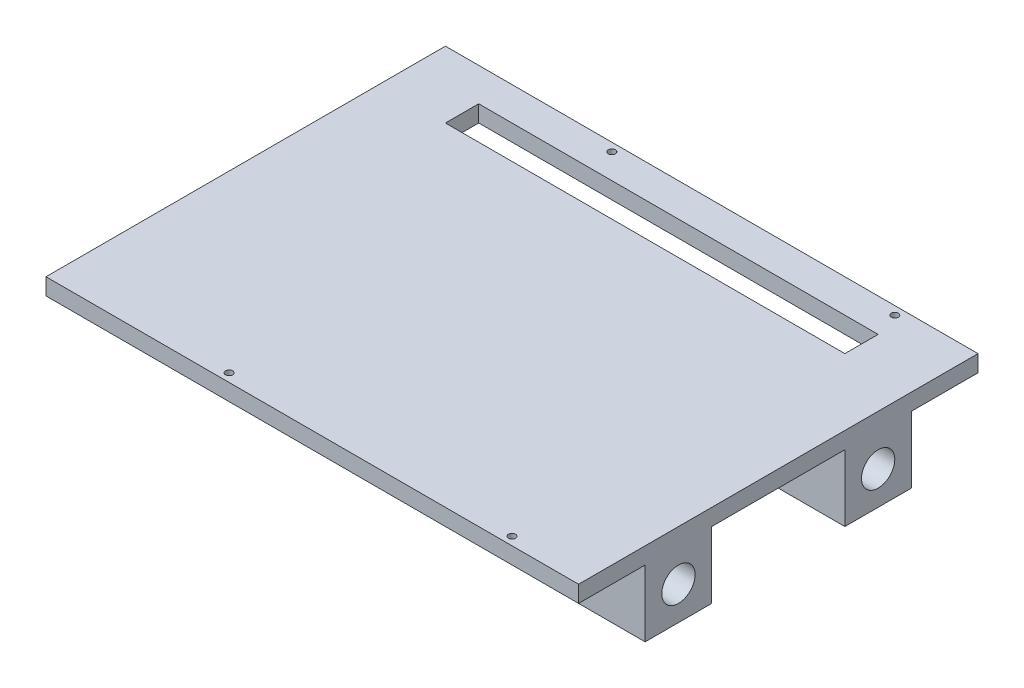
SolidWorks part; units mm, degrees
ref_plane "Front Plane" through (0, 0, 0) normal (0, 0, 1) x (1, 0, 0)
ref_plane "Top Plane" through (0, 0, 0) normal (0, 1, 0) x (1, 0, 0)
ref_plane "Right Plane" through (0, 0, 0) normal (1, 0, 0) x (0, 0, -1)
sketch "Sketch2" plane through (0, 0, 0) normal (0, 1, 0) x (1, 0, 0)
  line L1 (-101.6, -76.2) -> (101.6, -76.2)
  line L2 (-101.6, -76.2) -> (-101.6, 76.2)
  line L3 (-101.6, 76.2) -> (101.6, 76.2)
  line L4 (101.6, -76.2) -> (101.6, 76.2)
  line L5 (-101.6, -76.2) -> (101.6, 76.2) construction
  line L6 (-101.6, 76.2) -> (101.6, -76.2) construction
  point P0 (0, 0)
  dimension "D1" = 203.2
  dimension "D2" = 152.4
extrude "Boss-Extrude1" add sketch "Sketch2" along normal blind 6.35
sketch "Sketch3" plane through (0, 6.35, 0) normal (0, 1, 0) x (1, 0, 0)
  line L0 (-101.6, 0) -> (101.6, 0) construction
  line L1 (-101.6, 76.2) -> (-101.6, -76.2) construction
  line L2 (101.6, -76.2) -> (101.6, 76.2) construction
  line L3 (0, 76.2) -> (0, -76.2) construction
  line L4 (101.6, 76.2) -> (-101.6, 76.2) construction
  line L5 (-101.6, -76.2) -> (101.6, -76.2) construction
  line L7 (-76.2, 63.5) -> (76.2, 63.5)
  line L8 (-76.2, 63.5) -> (-76.2, 50.8)
  line L9 (-76.2, 50.8) -> (76.2, 50.8)
  line L10 (76.2, 63.5) -> (76.2, 50.8)
  line L11 (-76.2, 63.5) -> (76.2, 50.8) construction
  line L12 (-76.2, 50.8) -> (76.2, 63.5) construction
  point P12 (0, 57.15)
  dimension "D1" = 12.7
  dimension "D2" = 152.4
  dimension "D3" = 12.7
extrude "Cut-Extrude1" cut sketch "Sketch3" against normal blind 6.35
sketch "Sketch4" plane through (0, 0, 0) normal (0, -1, 0) x (1, 0, 0)
  line L0 (-101.6, -76.2) -> (-101.6, 76.2) construction
  line L1 (-101.6, 50.8) -> (-50.8, 50.8)
  line L2 (-101.6, 50.8) -> (-101.6, 25.4)
  line L3 (-101.6, 25.4) -> (-50.8, 25.4)
  line L4 (-50.8, 50.8) -> (-50.8, 25.4)
  line L5 (0, 76.2) -> (0, -76.2) construction
  line L6 (-101.6, 76.2) -> (101.6, 76.2) construction
  line L7 (101.6, -76.2) -> (-101.6, -76.2) construction
  line L8 (-101.6, 0) -> (101.6, 0) construction
  line L9 (101.6, 76.2) -> (101.6, -76.2) construction
  line L10 (101.6, 25.4) -> (50.8, 25.4)
  line L11 (50.8, 50.8) -> (50.8, 25.4)
  line L12 (101.6, 50.8) -> (50.8, 50.8)
  line L13 (101.6, 50.8) -> (101.6, 25.4)
  line L14 (101.6, -50.8) -> (101.6, -25.4)
  line L15 (101.6, -50.8) -> (50.8, -50.8)
  line L16 (50.8, -50.8) -> (50.8, -25.4)
  line L17 (101.6, -25.4) -> (50.8, -25.4)
  line L18 (-101.6, -25.4) -> (-50.8, -25.4)
  line L19 (-50.8, -50.8) -> (-50.8, -25.4)
  line L20 (-101.6, -50.8) -> (-50.8, -50.8)
  line L21 (-101.6, -50.8) -> (-101.6, -25.4)
  dimension "D1" = 25.4
  dimension "D2" = 50.8
  dimension "D3" = 25.4
sketch "Sketch6" plane through (0, 0, 0) normal (0, -1, 0) x (1, 0, 0)
  line L0 (0, -50.8) -> (0, -63.5) construction
  line L1 (-76.2, -50.8) -> (76.2, -50.8) construction
  line L2 (76.2, -63.5) -> (-76.2, -63.5) construction
extrude "Boss-Extrude2" add sketch "Sketch4" along normal blind 25.4
sketch "Sketch7" plane through (-101.6, 0, 0) normal (-1, 0, 0) x (0, 0, 1)
  line L0 (-38.1, -25.4) -> (-38.1, 6.35) construction
  line L1 (-25.4, -25.4) -> (-50.8, -25.4) construction
  line L2 (-76.2, 6.35) -> (76.2, 6.35) construction
  line L3 (-50.8, -12.7) -> (-25.4, -12.7) construction
  line L4 (-50.8, -25.4) -> (-50.8, 0) construction
  line L5 (-25.4, -25.4) -> (-25.4, 0) construction
  line L6 (38.1, -25.4) -> (38.1, 6.35) construction
  line L7 (50.8, -25.4) -> (25.4, -25.4) construction
  line L8 (25.4, -12.7) -> (50.8, -12.7) construction
  line L9 (25.4, -25.4) -> (25.4, 0) construction
  line L10 (50.8, -25.4) -> (50.8, 0) construction
  circle A0 centre (-38.1, -12.7) radius 6.35
  circle A1 centre (38.1, -12.7) radius 6.35
  dimension "D1" = 12.7
  dimension "D2" = 12.7
extrude "Cut-Extrude2" cut sketch "Sketch7" against normal blind 50.8
sketch "Sketch8" plane through (101.6, 0, 0) normal (1, 0, 0) x (0, 0, -1)
  line L0 (-50.8, -12.7) -> (50.8, -12.7) construction
  line L1 (-50.8, -25.4) -> (-50.8, 0) construction
  line L2 (50.8, -25.4) -> (50.8, 0) construction
  line L3 (-38.1, -25.4) -> (-38.1, 6.35) construction
  line L4 (50.8, -25.4) -> (25.4, -25.4) construction
  line L5 (38.1, -25.4) -> (38.1, 6.35) construction
  line L6 (-76.2, 6.35) -> (76.2, 6.35) construction
  line L7 (-25.4, -25.4) -> (-50.8, -25.4) construction
  circle A0 centre (-38.1, -12.7) radius 6.35
  circle A1 centre (38.1, -12.7) radius 6.35
  dimension "D1" = 12.7
  dimension "D2" = 12.7
extrude "Cut-Extrude3" cut sketch "Sketch8" against normal blind 50.8
ref_plane "Plane1" through (0, 0, 0) normal (-1, 0, 0) x (0, 0, 1)
ref_point "Point1"
sketch "Sketch12" plane through (0, 6.35, 0) normal (0, 1, 0) x (1, 0, 0)
  line L0 (101.6, 76.2) -> (-101.6, 76.2) construction
  line L1 (-38.1204, 76.2) -> (25.3796, 76.2)
  line L2 (-38.1204, 76.2) -> (-38.1204, 63.5)
  line L3 (-38.1204, 63.5) -> (25.3796, 63.5)
  line L4 (25.3796, 76.2) -> (25.3796, 63.5)
  line L5 (76.2, 63.5) -> (-76.2, 63.5) construction
  dimension "D1" = 63.5
hole_wizard "#6-32 Tapped Hole1" positions "Sketch13" profile "Sketch14" tap size "#6-32" standard "ANSI Inch"
sketch "Sketch13" plane through (0, 6.35, 0) normal (0, 1, 0) x (1, 0, 0)
  point P12 (-34.925, -73.025)
  point P15 (-34.925, 73.025)
  point P18 (73.025, 73.025)
  point P21 (73.025, -73.025)
cosmetic thread "Hole Thread6"
cosmetic thread "Hole Thread7"
cosmetic thread "Hole Thread8"
cosmetic thread "Hole Thread9"
sketch "Sketch14" plane through (-34.925, 6.35, 73.025) normal (1, 0, 0) x (0, 0, 1)
  line L0 (0, 0) -> (0, 13.5127)
  line L1 (0, 13.5127) -> (1.3525, 12.7)
  line L2 (1.3525, 12.7) -> (1.3525, 0)
  line L5 (1.3525, 0) -> (0, 0)
  line L10 (0, 13.5127) -> (-1.3526, 12.7) construction
  line L11 (0, -6.35) -> (0, 107.95) construction
  dimension "Tap Drill Dia." = 2.7051
  dimension "Tap Drill Depth" = 12.7
  dimension "Drill Angle" = 118
